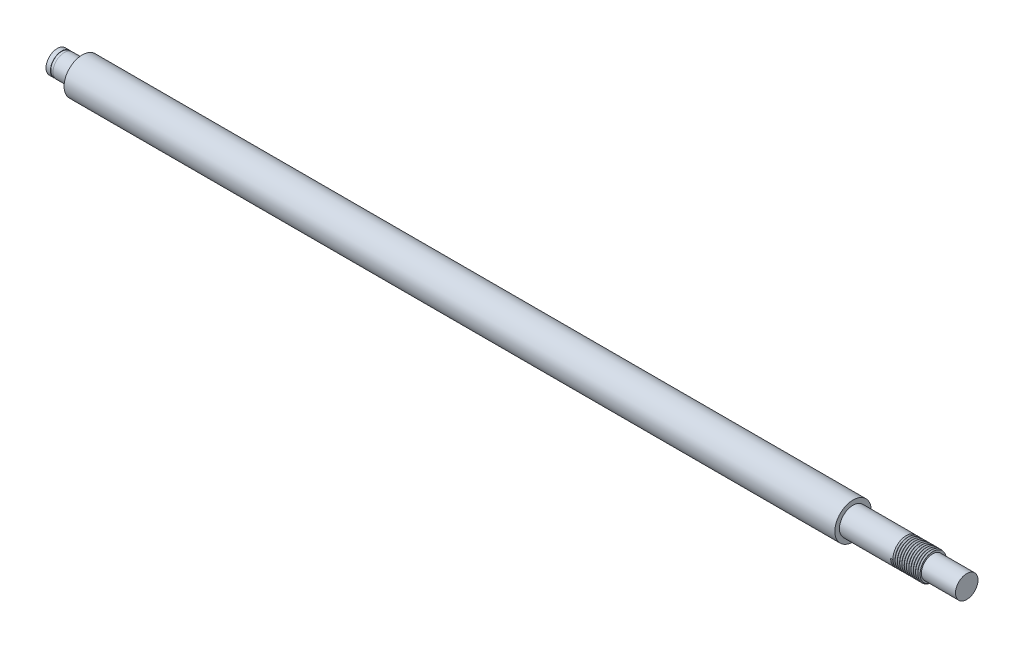
SolidWorks part; units mm, degrees
material "Хромистая нержавеющая сталь"
ref_plane "Спереди" through (0, 0, 0) normal (0, 0, 1) x (1, 0, 0)
ref_plane "Сверху" through (0, 0, 0) normal (0, 1, 0) x (1, 0, 0)
ref_plane "Справа" through (0, 0, 0) normal (1, 0, 0) x (0, 0, -1)
sketch "Эскиз1" plane through (0, 0, 0) normal (0, 0, 1) x (1, 0, 0)
  line L0 (-310.0019, 5.9419) -> (-310.0019, 10.8919)
  line L1 (-310.0019, 10.8919) -> (-308.0519, 10.8919)
  line L2 (-308.0519, 10.8919) -> (-308.0519, 10.7419)
  line L3 (-308.0519, 10.7419) -> (-306.9019, 10.7419)
  line L4 (-306.9019, 10.7419) -> (-306.9019, 10.8919)
  line L5 (-306.9019, 10.8919) -> (-299.0019, 10.8919)
  line L6 (-299.0019, 10.8919) -> (-299.0019, 13.9419)
  line L7 (-299.0019, 13.9419) -> (39.9981, 13.9419)
  line L8 (39.9981, 13.9419) -> (39.9981, 11.9419)
  line L9 (39.9981, 11.9419) -> (74.9981, 11.9419)
  line L10 (74.9981, 11.9419) -> (74.9981, 10.8919)
  line L11 (74.9981, 10.8919) -> (89.9981, 10.8919)
  line L12 (89.9981, 10.8919) -> (89.9981, 5.9419)
  line L13 (89.9981, 5.9419) -> (-310.0019, 5.9419)
  line L14 (60.9981, 14.6846) -> (60.9981, -1.3142) construction
  dimension "D1" = 1.15
  dimension "D2" = 7.9
  dimension "D3" = 11
  dimension "D4" = 35
  dimension "D5" = 50
  dimension "D6" = 14
  dimension "D7" = 4.95
  dimension "D8" = 1.05
  dimension "D9" = 2
  dimension "D10" = 4.95
  dimension "D11" = 4.8
  dimension "D12" = 4.95
  dimension "D13" = 400
revolve "Повернуть1" add sketch "Эскиз1" angle 360 about L13
ref_plane "Плоскость1" through (49.9981, 0, 0) normal (1, 0, 0) x (0, 0, -1)
sketch "Эскиз2" plane through (49.9981, 0, 0) normal (1, 0, 0) x (0, 0, -1)
  circle A0 centre (0, 5.9419) radius 8 construction
  circle A1 centre (0, 5.9419) radius 8
curve "Спираль1" pitch 5 height 290 turns 58
sketch "Эскиз3" plane through (0, 0, 0) normal (0, 0, 1) x (1, 0, 0)
  line L0 (-207.8405, -2.5666) -> (-201.4949, -2.5666) construction
  line L1 (-210.2778, -2.0666) -> (-203.5838, -2.0666) construction
  line L2 (-207.8405, -4.8575) -> (-207.8405, -1.8666) construction
  line L3 (-205.3405, -4.8575) -> (-205.3405, -0.2923) construction
  line L4 (-205.3405, -1.8666) -> (-205.4905, -2.0666)
  line L5 (-205.4905, -2.0666) -> (-205.4905, -2.5666)
  line L6 (-205.4905, -2.5666) -> (-205.1905, -2.5666)
  line L7 (-205.1905, -2.5666) -> (-205.1905, -2.0666)
  line L8 (-205.1905, -2.0666) -> (-205.3405, -1.8666)
  circle A0 centre (-207.8405, -2.5666) radius 1.5875
  point P7 (-207.7498, -2.0666)
  dimension "D1" = 3.175
  dimension "D2" = 0.5
  dimension "D3" = 2.5
  dimension "D4" = 0.2
  dimension "D5" = 0.3
ref_plane "Плоскость2" through (84.9981, 0, 0) normal (1, 0, 0) x (0, 0, -1)
sketch "Эскиз4" plane through (84.9981, 0, 0) normal (1, 0, 0) x (0, 0, -1)
  circle A0 centre (0, 5.9419) radius 6 construction
  circle A1 centre (0, 5.9419) radius 6
curve "Спираль2" pitch 1 height 22 radius 6 centre (84.9981, 5.9419, 0) axis (-1, 0, 0) start towards (0, 0, 1)
sketch "Эскиз5" plane through (0, 0, 0) normal (0, 0, 1) x (1, 0, 0)
  line L0 (76.2561, 0.4419) -> (75.7561, -0.0581)
  line L1 (39.9981, -0.0581) -> (74.9981, -0.0581) construction
  line L2 (75.7561, -0.0581) -> (75.7561, -1.0581)
  line L3 (75.7561, -1.0581) -> (76.7561, -1.0581)
  line L4 (76.7561, -1.0581) -> (76.7561, -0.0581)
  line L5 (76.7561, -0.0581) -> (76.2561, 0.4419)
  line L6 (76.2561, 0.4419) -> (76.2561, -0.2584) construction
  line L7 (75.7561, -0.0581) -> (76.7561, -0.0581) construction
  dimension "D1" = 0.5
  dimension "D2" = 1
  dimension "D3" = 1
sweep "Вырез-По траектории7" cut profiles "Эскиз5" path "Спираль2" align with end faces yes
